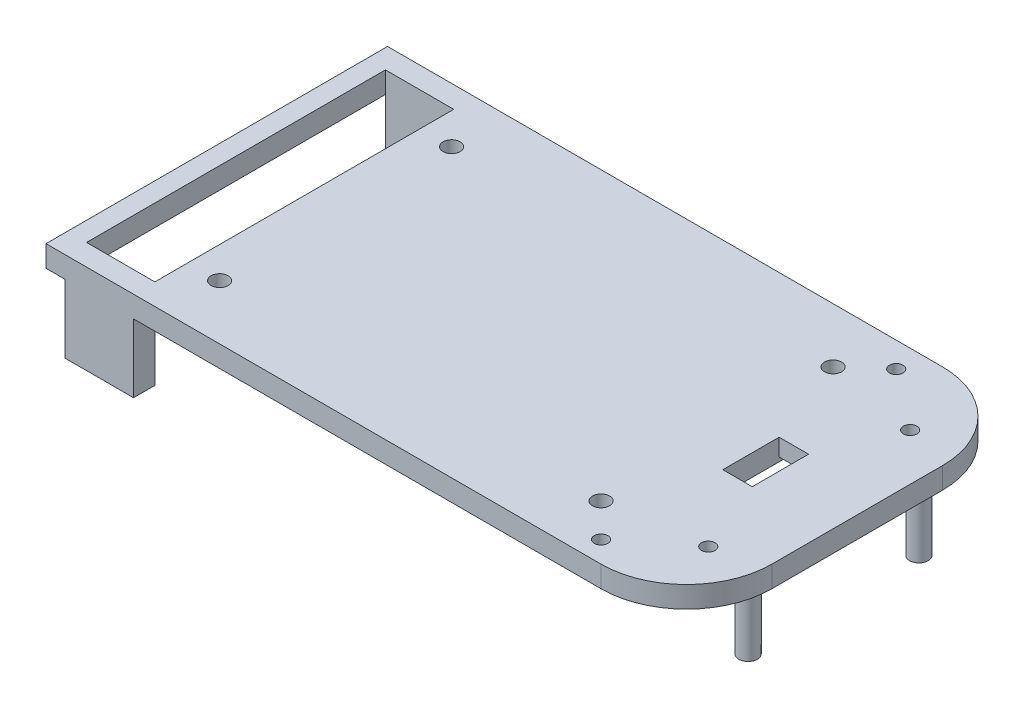
SolidWorks part; units mm, degrees
note: The reader was unsure of these and kept them because the rebuilt part matched: shared geometry of "Croquis2<3>", "Croquis4<3>".
ref_plane "Front Plane" through (0, 0, 0) normal (0, 0, 1) x (1, 0, 0)
ref_plane "Top Plane" through (0, 0, 0) normal (0, 1, 0) x (1, 0, 0)
ref_plane "Right Plane" through (0, 0, 0) normal (1, 0, 0) x (0, 0, -1)
sketch "Croquis2" plane through (0, 0, 0) normal (0, 1, 0) x (1, 0, 0)
  line L0 (45, 0) -> (46.0553, 0) construction
  line L1 (-75, -40) -> (55, -40)
  line L2 (-75, -40) -> (-75, 40)
  line L3 (-75, 40) -> (55, 40)
  line L4 (75, -20) -> (75, 20)
  line L5 (45, 0) -> (46.0553, 0) construction
  line L6 (67, 26.7583) -> (67, -26.7583)
  line L7 (45, -30) -> (-50, -30)
  line L8 (45, -30) -> (45, 30)
  line L9 (45, 30) -> (-50, 30)
  line L10 (-50, -30) -> (-50, 30)
  line L11 (67, -26.7583) -> (67, 26.7583)
  line L13 (67, 26.7583) -> (61, 26.7583)
  line L15 (46.228, -1.6) -> (46.2586, -1.7343)
  line L16 (61.1553, 0) -> (61.0553, 0) construction
  line L17 (54.1602, 2.3742) -> (54.0439, 2.2986)
  line L18 (54.0439, 2.2986) -> (53.9684, 2.4149)
  line L19 (53.9087, 2.4244) -> (53.801, 2.3371)
  line L20 (53.801, 2.3371) -> (53.7137, 2.4449)
  line L21 (53.6534, 2.448) -> (53.5553, 2.35)
  line L22 (53.5553, 2.35) -> (53.4573, 2.448)
  line L23 (53.3969, 2.4449) -> (53.3097, 2.3371)
  line L24 (53.3097, 2.3371) -> (53.2019, 2.4244)
  line L25 (53.1422, 2.4149) -> (53.0667, 2.2986)
  line L26 (53.0667, 2.2986) -> (52.9505, 2.3742)
  line L27 (52.8921, 2.3585) -> (52.8291, 2.235)
  line L28 (52.8291, 2.235) -> (52.7056, 2.2979)
  line L29 (52.6492, 2.2763) -> (52.5995, 2.1468)
  line L30 (52.5995, 2.1468) -> (52.4701, 2.1965)
  line L31 (52.4162, 2.1691) -> (52.3803, 2.0352)
  line L32 (52.3803, 2.0352) -> (52.2464, 2.071)
  line L33 (52.1957, 2.0381) -> (52.174, 1.9012)
  line L34 (52.174, 1.9012) -> (52.0371, 1.9229)
  line L35 (51.9901, 1.8848) -> (51.9829, 1.7464)
  line L36 (51.9829, 1.7464) -> (51.8444, 1.7536)
  line L37 (51.8017, 1.7109) -> (51.8089, 1.5725)
  line L38 (51.8089, 1.5725) -> (51.6705, 1.5652)
  line L39 (51.6325, 1.5182) -> (51.6541, 1.3813)
  line L40 (51.6541, 1.3813) -> (51.5172, 1.3596)
  line L41 (51.4843, 1.3089) -> (51.5202, 1.175)
  line L42 (51.5202, 1.175) -> (51.3862, 1.1391)
  line L43 (51.3588, 1.0853) -> (51.4085, 0.9558)
  line L44 (51.4085, 0.9558) -> (51.2791, 0.9061)
  line L45 (51.2574, 0.8497) -> (51.3203, 0.7262)
  line L46 (51.3203, 0.7262) -> (51.1968, 0.6632)
  line L47 (51.1812, 0.6049) -> (51.2567, 0.4886)
  line L48 (51.2567, 0.4886) -> (51.1404, 0.4131)
  line L49 (51.1309, 0.3534) -> (51.2182, 0.2456)
  line L50 (51.2182, 0.2456) -> (51.1105, 0.1584)
  line L51 (51.1073, 0.098) -> (51.2053, 0)
  line L52 (51.2053, 0) -> (51.1073, -0.098)
  line L53 (51.1105, -0.1584) -> (51.2182, -0.2456)
  line L54 (51.2182, -0.2456) -> (51.1309, -0.3534)
  line L55 (51.1404, -0.4131) -> (51.2567, -0.4886)
  line L56 (51.2567, -0.4886) -> (51.1812, -0.6049)
  line L57 (51.1968, -0.6632) -> (51.3203, -0.7262)
  line L58 (51.3203, -0.7262) -> (51.2574, -0.8497)
  line L59 (51.2791, -0.9061) -> (51.4085, -0.9558)
  line L60 (51.4085, -0.9558) -> (51.3588, -1.0853)
  line L61 (51.3862, -1.1391) -> (51.5202, -1.175)
  line L62 (51.5202, -1.175) -> (51.4843, -1.3089)
  line L63 (51.5172, -1.3596) -> (51.6541, -1.3813)
  line L64 (51.6541, -1.3813) -> (51.6325, -1.5182)
  line L65 (51.6705, -1.5652) -> (51.8089, -1.5725)
  line L66 (51.8089, -1.5725) -> (51.8017, -1.7109)
  line L67 (51.8444, -1.7536) -> (51.9829, -1.7464)
  line L68 (51.9829, -1.7464) -> (51.9901, -1.8848)
  line L69 (52.0371, -1.9229) -> (52.174, -1.9012)
  line L70 (52.174, -1.9012) -> (52.1957, -2.0381)
  line L71 (52.2464, -2.071) -> (52.3803, -2.0352)
  line L72 (52.3803, -2.0352) -> (52.4162, -2.1691)
  line L73 (52.4701, -2.1965) -> (52.5995, -2.1468)
  line L74 (52.5995, -2.1468) -> (52.6492, -2.2763)
  line L75 (52.7056, -2.2979) -> (52.8291, -2.235)
  line L76 (52.8291, -2.235) -> (52.8921, -2.3585)
  line L77 (52.9505, -2.3742) -> (53.0667, -2.2986)
  line L78 (53.0667, -2.2986) -> (53.1422, -2.4149)
  line L79 (53.2019, -2.4244) -> (53.3097, -2.3371)
  line L80 (53.3097, -2.3371) -> (53.3969, -2.4449)
  line L81 (53.4573, -2.448) -> (53.5553, -2.35)
  line L82 (53.5553, -2.35) -> (53.6534, -2.448)
  line L83 (53.7137, -2.4449) -> (53.801, -2.3371)
  line L84 (53.801, -2.3371) -> (53.9087, -2.4244)
  line L85 (53.9684, -2.4149) -> (54.0439, -2.2986)
  line L86 (54.0439, -2.2986) -> (54.1602, -2.3742)
  line L87 (54.2186, -2.3585) -> (54.2815, -2.235)
  line L88 (54.2815, -2.235) -> (54.4051, -2.2979)
  line L89 (54.4615, -2.2763) -> (54.5112, -2.1468)
  line L90 (54.5112, -2.1468) -> (54.6406, -2.1965)
  line L91 (54.6944, -2.1691) -> (54.7303, -2.0352)
  line L92 (54.7303, -2.0352) -> (54.8643, -2.071)
  line L93 (54.9149, -2.0381) -> (54.9366, -1.9012)
  line L94 (54.9366, -1.9012) -> (55.0736, -1.9229)
  line L95 (55.1205, -1.8848) -> (55.1278, -1.7464)
  line L96 (55.1278, -1.7464) -> (55.2662, -1.7536)
  line L97 (55.309, -1.7109) -> (55.3017, -1.5725)
  line L98 (55.3017, -1.5725) -> (55.4402, -1.5652)
  line L99 (55.4782, -1.5182) -> (55.4565, -1.3813)
  line L100 (55.4565, -1.3813) -> (55.5935, -1.3596)
  line L101 (55.6264, -1.3089) -> (55.5905, -1.175)
  line L102 (55.5905, -1.175) -> (55.7244, -1.1391)
  line L103 (55.7518, -1.0853) -> (55.7022, -0.9558)
  line L104 (55.7022, -0.9558) -> (55.8316, -0.9061)
  line L105 (55.8533, -0.8497) -> (55.7903, -0.7262)
  line L106 (55.7903, -0.7262) -> (55.9138, -0.6632)
  line L107 (55.9295, -0.6049) -> (55.854, -0.4886)
  line L108 (55.854, -0.4886) -> (55.9703, -0.4131)
  line L109 (55.9797, -0.3534) -> (55.8925, -0.2456)
  line L110 (55.8925, -0.2456) -> (56.0002, -0.1584)
  line L111 (56.0034, -0.098) -> (55.9053, 0)
  line L112 (55.9053, 0) -> (56.0034, 0.098)
  line L113 (56.0002, 0.1584) -> (55.8925, 0.2456)
  line L114 (55.8925, 0.2456) -> (55.9797, 0.3534)
  line L115 (55.9703, 0.4131) -> (55.854, 0.4886)
  line L116 (55.854, 0.4886) -> (55.9295, 0.6049)
  line L117 (55.9138, 0.6632) -> (55.7903, 0.7262)
  line L118 (55.7903, 0.7262) -> (55.8533, 0.8497)
  line L119 (55.8316, 0.9061) -> (55.7022, 0.9558)
  line L120 (55.7022, 0.9558) -> (55.7518, 1.0853)
  line L121 (55.7244, 1.1391) -> (55.5905, 1.175)
  line L122 (55.5905, 1.175) -> (55.6264, 1.3089)
  line L123 (55.5935, 1.3596) -> (55.4565, 1.3813)
  line L124 (55.4565, 1.3813) -> (55.4782, 1.5182)
  line L125 (55.4402, 1.5652) -> (55.3017, 1.5725)
  line L126 (55.3017, 1.5725) -> (55.309, 1.7109)
  line L127 (55.2662, 1.7536) -> (55.1278, 1.7464)
  line L128 (55.1278, 1.7464) -> (55.1205, 1.8848)
  line L129 (55.0736, 1.9229) -> (54.9366, 1.9012)
  line L130 (54.9366, 1.9012) -> (54.9149, 2.0381)
  line L131 (54.8643, 2.071) -> (54.7303, 2.0352)
  line L132 (54.7303, 2.0352) -> (54.6944, 2.1691)
  line L133 (54.6406, 2.1965) -> (54.5112, 2.1468)
  line L134 (54.5112, 2.1468) -> (54.4615, 2.2763)
  line L135 (54.4051, 2.2979) -> (54.2815, 2.235)
  line L136 (54.2815, 2.235) -> (54.2186, 2.3585)
  line L137 (53.5553, 0) -> (53.5553, -7.5) construction
  line L139 (65.0006, 25.8237) -> (59.5501, 25.8237) construction
  line L141 (61.0553, 0) -> (67, 0) construction
  line L142 (59.0553, 0) -> (53.5553, 0) construction
  line L143 (48.0553, 0) -> (53.5553, 0) construction
  line L144 (48.0553, 0) -> (59.0553, 0) construction
  line L145 (60.701, 2.278) -> (60.8827, 1.6)
  line L146 (61, 24.889) -> (61, 23.889)
  line L149 (61, 22.0197) -> (61, 21.0197)
  line L152 (61, 19.1504) -> (61, 18.1504)
  line L154 (59.5501, 17.5667) -> (59.5501, 16.8648)
  line L155 (61, 16.2811) -> (61, 15.2811)
  line L157 (59.5501, 14.6974) -> (59.5501, 13.9955)
  line L158 (61, 13.4118) -> (61, 12.4118)
  line L160 (59.5501, 11.8282) -> (59.5501, 11.1262)
  line L161 (61, 10.5425) -> (61, 9.5425)
  line L163 (59.5501, 8.9589) -> (59.5501, 8.2569)
  line L164 (61, 7.6732) -> (61, 6.6732)
  line L166 (59.5501, 6.0896) -> (59.5501, 5.3876)
  line L167 (61, 4.8039) -> (61, 3.8039)
  line L169 (59.5501, 3.2203) -> (59.5501, 2.5183)
  line L170 (61, 1.9346) -> (61, 0.9346)
  line L172 (59.5501, 0.351) -> (59.5501, -0.351)
  line L173 (61, -0.9346) -> (61, -1.9346)
  line L175 (59.5501, -2.5183) -> (59.5501, -3.2203)
  line L176 (61, -3.8039) -> (61, -4.8039)
  line L178 (59.5501, -5.3876) -> (59.5501, -6.0896)
  line L179 (61, -6.6732) -> (61, -7.6732)
  line L181 (59.5501, -8.2569) -> (59.5501, -8.9589)
  line L182 (61, -9.5425) -> (61, -10.5425)
  line L184 (59.5501, -11.1262) -> (59.5501, -11.8282)
  line L185 (61, -12.4118) -> (61, -13.4118)
  line L187 (59.5501, -13.9955) -> (59.5501, -14.6974)
  line L188 (61, -15.2811) -> (61, -16.2811)
  line L190 (59.5501, -16.8648) -> (59.5501, -17.5667)
  line L191 (61, -18.1504) -> (61, -19.1504)
  line L194 (61, -21.0197) -> (61, -22.0197)
  line L197 (61, -23.889) -> (61, -24.889)
  line L200 (64, 26.7583) -> (64, 26.3977) construction
  line L203 (61, -26.7583) -> (67, -26.7583)
  line L204 (75, 20) -> (67, 20) construction
  line L205 (61, -26.7583) -> (61, -27.7583) [skipped]
  line L206 (-50, 0) -> (-75, 0) construction
  line L207 (75, -20) -> (67, -20) construction
  line L208 (50, -40) -> (50, 40) construction
  line L209 (50, -35) -> (50, -43.5216) construction
  line L210 (53.5731, -35) -> (53.5731, -43.5216)
  line L211 (46.4269, -35) -> (46.4269, -43.5216)
  line L212 (50.0036, 34.1275) -> (50.0036, 40.0656) construction
  line L213 (53.6852, 34.1275) -> (53.5731, 43.5216)
  line L214 (46.4269, 35) -> (46.4269, 43.5216)
  line L215 (-50, -30) -> (-47.1716, -27.1716) construction
  line L221 (-50, -30) -> (-47.1716, -30)
  line L222 (-50, -30) -> (-50, -27.1716)
  line L223 (46.4269, -43.5216) -> (46.4269, -48.5216)
  line L224 (53.5731, -43.5216) -> (53.5731, -48.5216)
  line L225 (46.4269, -48.5216) -> (53.5731, -48.5216)
  line L226 (53.5731, 43.5216) -> (53.5731, 48.5216)
  line L227 (46.4269, 43.5216) -> (46.4269, 48.5216)
  line L228 (46.4269, 48.5216) -> (53.5731, 48.5216)
  line L229 (50, 43.0304) -> (64, 23.3977) construction
  line L232 (46.4269, 48.5216) -> (53.5731, 48.5216)
  line L233 (46.4269, 48.5216) -> (46.4269, 46.5216)
  line L234 (53.5731, 48.5216) -> (53.5731, 46.5216)
  line L235 (46.4269, 46.5216) -> (53.5731, 46.5216)
  line L236 (46.4269, -46.5216) -> (53.5731, -46.5216)
  line L239 (61, 19.1504) -> (67, 19.1504)
  line L240 (61, 26.7583) -> (61, 19.1504)
  line L241 (50.0036, 40.0656) -> (61.1732, 24.4022)
  line L242 (52.8363, 42.0529) -> (64, 26.3977)
  line L243 (48.6009, 42.0327) -> (62.6009, 22.4) construction
  line L244 (51.4182, 44.0416) -> (65.4182, 24.409) construction
  line L245 (61, 24.889) -> (61, 26.7583)
  line L246 (64, 25.8237) -> (64, -26.7583) construction
  line L248 (-70.5, -35) -> (-54.5, -35)
  line L249 (61, -26.7583) -> (61, -19.1504)
  line L250 (61, -19.1504) -> (67, -19.1504)
  line L251 (-50, -27.1716) -> (-47.1716, -27.1716)
  line L252 (-47.1716, -30) -> (-47.1716, -27.1716)
  line L253 (-2.5, -30) -> (-2.5, 30) construction
  line L254 (-70.5, -35) -> (-70.5, -40)
  line L255 (-54.5, 35) -> (-70.5, 35)
  line L260 (-54.5, 35) -> (-54.5, -35)
  line L261 (-54.5, -35) -> (-70.5, -35)
  line L262 (-70.5, 35) -> (-70.5, -35)
  line L263 (-54.5, 35) -> (-70.5, -35) construction
  line L264 (-54.5, -35) -> (-70.5, 35) construction
  line L265 (-70.5, -40) -> (-54.5, -40)
  line L266 (-54.5, -35) -> (-54.5, -40)
  line L267 (-70.5, 35) -> (-54.5, 35)
  line L268 (-70.5, 35) -> (-70.5, 40)
  line L269 (-70.5, 40) -> (-54.5, 40)
  line L270 (-54.5, 35) -> (-54.5, 40)
  circle A0 centre (53.5553, 0) radius 7.5
  arc A1 (53.9684, 2.4149) -> (53.9087, 2.4244) centre (53.5553, 0) ccw
  arc A2 (53.7137, 2.4449) -> (53.6534, 2.448) centre (53.5553, 0) ccw
  arc A3 (53.4573, 2.448) -> (53.3969, 2.4449) centre (53.5553, 0) ccw
  arc A4 (53.2019, 2.4244) -> (53.1422, 2.4149) centre (53.5553, 0) ccw
  arc A5 (52.9505, 2.3742) -> (52.8921, 2.3585) centre (53.5553, 0) ccw
  arc A6 (52.7056, 2.2979) -> (52.6492, 2.2763) centre (53.5553, 0) ccw
  arc A7 (52.4701, 2.1965) -> (52.4162, 2.1691) centre (53.5553, 0) ccw
  arc A8 (52.2464, 2.071) -> (52.1957, 2.0381) centre (53.5553, 0) ccw
  arc A9 (52.0371, 1.9229) -> (51.9901, 1.8848) centre (53.5553, 0) ccw
  arc A10 (51.8444, 1.7536) -> (51.8017, 1.7109) centre (53.5553, 0) ccw
  arc A11 (51.6705, 1.5652) -> (51.6325, 1.5182) centre (53.5553, 0) ccw
  arc A12 (51.5172, 1.3596) -> (51.4843, 1.3089) centre (53.5553, 0) ccw
  arc A13 (51.3862, 1.1391) -> (51.3588, 1.0853) centre (53.5553, 0) ccw
  arc A14 (51.2791, 0.9061) -> (51.2574, 0.8497) centre (53.5553, 0) ccw
  arc A15 (51.1968, 0.6632) -> (51.1812, 0.6049) centre (53.5553, 0) ccw
  arc A16 (51.1404, 0.4131) -> (51.1309, 0.3534) centre (53.5553, 0) ccw
  arc A17 (51.1105, 0.1584) -> (51.1073, 0.098) centre (53.5553, 0) ccw
  arc A18 (51.1073, -0.098) -> (51.1105, -0.1584) centre (53.5553, 0) ccw
  arc A19 (51.1309, -0.3534) -> (51.1404, -0.4131) centre (53.5553, 0) ccw
  arc A20 (51.1812, -0.6049) -> (51.1968, -0.6632) centre (53.5553, 0) ccw
  arc A21 (51.2574, -0.8497) -> (51.2791, -0.9061) centre (53.5553, 0) ccw
  arc A22 (51.3588, -1.0853) -> (51.3862, -1.1391) centre (53.5553, 0) ccw
  arc A23 (51.4843, -1.3089) -> (51.5172, -1.3596) centre (53.5553, 0) ccw
  arc A24 (51.6325, -1.5182) -> (51.6705, -1.5652) centre (53.5553, 0) ccw
  arc A25 (51.8017, -1.7109) -> (51.8444, -1.7536) centre (53.5553, 0) ccw
  arc A26 (51.9901, -1.8848) -> (52.0371, -1.9229) centre (53.5553, 0) ccw
  arc A27 (52.1957, -2.0381) -> (52.2464, -2.071) centre (53.5553, 0) ccw
  arc A28 (52.4162, -2.1691) -> (52.4701, -2.1965) centre (53.5553, 0) ccw
  arc A29 (52.6492, -2.2763) -> (52.7056, -2.2979) centre (53.5553, 0) ccw
  arc A30 (52.8921, -2.3585) -> (52.9505, -2.3742) centre (53.5553, 0) ccw
  arc A31 (53.1422, -2.4149) -> (53.2019, -2.4244) centre (53.5553, 0) ccw
  arc A32 (53.3969, -2.4449) -> (53.4573, -2.448) centre (53.5553, 0) ccw
  arc A33 (53.6534, -2.448) -> (53.7137, -2.4449) centre (53.5553, 0) ccw
  arc A34 (53.9087, -2.4244) -> (53.9684, -2.4149) centre (53.5553, 0) ccw
  arc A35 (54.1602, -2.3742) -> (54.2186, -2.3585) centre (53.5553, 0) ccw
  arc A36 (54.4051, -2.2979) -> (54.4615, -2.2763) centre (53.5553, 0) ccw
  arc A37 (54.6406, -2.1965) -> (54.6944, -2.1691) centre (53.5553, 0) ccw
  arc A38 (54.8643, -2.071) -> (54.9149, -2.0381) centre (53.5553, 0) ccw
  arc A39 (55.0736, -1.9229) -> (55.1205, -1.8848) centre (53.5553, 0) ccw
  arc A40 (55.2662, -1.7536) -> (55.309, -1.7109) centre (53.5553, 0) ccw
  arc A41 (55.4402, -1.5652) -> (55.4782, -1.5182) centre (53.5553, 0) ccw
  arc A42 (55.5935, -1.3596) -> (55.6264, -1.3089) centre (53.5553, 0) ccw
  arc A43 (55.7244, -1.1391) -> (55.7518, -1.0853) centre (53.5553, 0) ccw
  arc A44 (55.8316, -0.9061) -> (55.8533, -0.8497) centre (53.5553, 0) ccw
  arc A45 (55.9138, -0.6632) -> (55.9295, -0.6049) centre (53.5553, 0) ccw
  arc A46 (55.9703, -0.4131) -> (55.9797, -0.3534) centre (53.5553, 0) ccw
  arc A47 (56.0002, -0.1584) -> (56.0034, -0.098) centre (53.5553, 0) ccw
  arc A48 (56.0034, 0.098) -> (56.0002, 0.1584) centre (53.5553, 0) ccw
  arc A49 (55.9797, 0.3534) -> (55.9703, 0.4131) centre (53.5553, 0) ccw
  arc A50 (55.9295, 0.6049) -> (55.9138, 0.6632) centre (53.5553, 0) ccw
  arc A51 (55.8533, 0.8497) -> (55.8316, 0.9061) centre (53.5553, 0) ccw
  arc A52 (55.7518, 1.0853) -> (55.7244, 1.1391) centre (53.5553, 0) ccw
  arc A53 (55.6264, 1.3089) -> (55.5935, 1.3596) centre (53.5553, 0) ccw
  arc A54 (55.4782, 1.5182) -> (55.4402, 1.5652) centre (53.5553, 0) ccw
  arc A55 (55.309, 1.7109) -> (55.2662, 1.7536) centre (53.5553, 0) ccw
  arc A56 (55.1205, 1.8848) -> (55.0736, 1.9229) centre (53.5553, 0) ccw
  arc A57 (54.9149, 2.0381) -> (54.8643, 2.071) centre (53.5553, 0) ccw
  arc A58 (54.6944, 2.1691) -> (54.6406, 2.1965) centre (53.5553, 0) ccw
  arc A59 (54.4615, 2.2763) -> (54.4051, 2.2979) centre (53.5553, 0) ccw
  arc A60 (54.2186, 2.3585) -> (54.1602, 2.3742) centre (53.5553, 0) ccw
  circle A61 centre (53.5553, 0) radius 2.25
  arc A62 (55, 40) -> (75, 20) centre (55, 20) cw
  arc A63 (55, -40) -> (75, -20) centre (55, -20) ccw
  circle A64 centre (53.5553, 0) radius 5.5
  arc A65 (54.0553, -5.4772) -> (55.1553, -7.3273) centre (59.6317, -3.4139) ccw
  arc A66 (53.0553, -5.4772) -> (51.9553, -7.3273) centre (47.479, -3.4139) cw
  arc A67 (50.3837, -4.4934) -> (48.506, -5.5457) centre (46.5861, 0.0817) cw
  arc A68 (51.2497, -4.9934) -> (51.2773, -7.1457) centre (57.1107, -5.9946) ccw
  arc A69 (48.5619, -2.3056) -> (46.4097, -2.278) centre (47.5607, 3.5553) cw
  arc A70 (49.0619, -3.1716) -> (48.0097, -5.0493) centre (53.637, -6.9692) ccw
  arc A71 (48.0781, 0.5) -> (46.228, 1.6) centre (50.1415, 6.0763) cw
  arc A72 (48.0781, -0.5) -> (46.228, -1.6) centre (50.1415, -6.0763) ccw
  arc A73 (49.0619, 3.1716) -> (48.0097, 5.0493) centre (53.637, 6.9692) cw
  arc A74 (48.5619, 2.3056) -> (46.4097, 2.278) centre (47.5607, -3.5553) ccw
  arc A75 (51.2497, 4.9934) -> (51.2773, 7.1457) centre (57.1107, 5.9946) cw
  arc A76 (50.3837, 4.4934) -> (48.506, 5.5457) centre (46.5861, -0.0817) ccw
  arc A77 (54.0553, 5.4772) -> (55.1553, 7.3273) centre (59.6317, 3.4139) cw
  arc A78 (53.0553, 5.4772) -> (51.9553, 7.3273) centre (47.479, 3.4139) ccw
  arc A79 (56.727, 4.4934) -> (58.6046, 5.5457) centre (60.5245, -0.0817) cw
  arc A80 (55.8609, 4.9934) -> (55.8334, 7.1457) centre (50, 5.9946) ccw
  arc A81 (58.5487, 2.3056) -> (60.701, 2.278) centre (59.55, -3.5553) cw
  arc A82 (58.0487, 3.1716) -> (59.101, 5.0493) centre (53.4736, 6.9692) ccw
  arc A83 (59.0326, -0.5) -> (60.8827, -1.6) centre (56.9692, -6.0763) cw
  arc A84 (59.0326, 0.5) -> (60.8827, 1.6) centre (56.9692, 6.0763) ccw
  arc A85 (58.0487, -3.1716) -> (59.101, -5.0493) centre (53.4736, -6.9692) cw
  arc A86 (58.5487, -2.3056) -> (60.701, -2.278) centre (59.55, 3.5553) ccw
  arc A89 (55.8609, -4.9934) -> (55.8334, -7.1457) centre (50, -5.9946) cw
  arc A90 (56.727, -4.4934) -> (58.6046, -5.5457) centre (60.5245, 0.0817) ccw
  arc A95 (61, 16.2811) -> (59.5501, 16.8648) centre (62.2327, 21.4358) cw
  arc A96 (61, 18.1504) -> (59.5501, 17.5667) centre (62.2327, 12.9958) ccw
  arc A97 (61, 13.4118) -> (59.5501, 13.9955) centre (62.2327, 18.5665) cw
  arc A98 (61, 15.2811) -> (59.5501, 14.6974) centre (62.2327, 10.1265) ccw
  arc A99 (61, 10.5425) -> (59.5501, 11.1262) centre (62.2327, 15.6972) cw
  arc A100 (61, 12.4118) -> (59.5501, 11.8282) centre (62.2327, 7.2572) ccw
  arc A101 (61, 7.6732) -> (59.5501, 8.2569) centre (62.2327, 12.8279) cw
  arc A102 (61, 9.5425) -> (59.5501, 8.9589) centre (62.2327, 4.3879) ccw
  arc A103 (61, 4.8039) -> (59.5501, 5.3876) centre (62.2327, 9.9586) cw
  arc A104 (61, 6.6732) -> (59.5501, 6.0896) centre (62.2327, 1.5186) ccw
  arc A105 (61, 1.9346) -> (59.5501, 2.5183) centre (62.2327, 7.0893) cw
  arc A106 (61, 3.8039) -> (59.5501, 3.2203) centre (62.2327, -1.3507) ccw
  arc A107 (61, -0.9346) -> (59.5501, -0.351) centre (62.2327, 4.22) cw
  arc A108 (61, 0.9346) -> (59.5501, 0.351) centre (62.2327, -4.22) ccw
  arc A109 (61, -3.8039) -> (59.5501, -3.2203) centre (62.2327, 1.3507) cw
  arc A110 (61, -1.9346) -> (59.5501, -2.5183) centre (62.2327, -7.0893) ccw
  arc A111 (61, -6.6732) -> (59.5501, -6.0896) centre (62.2327, -1.5186) cw
  arc A112 (61, -4.8039) -> (59.5501, -5.3876) centre (62.2327, -9.9586) ccw
  arc A113 (61, -9.5425) -> (59.5501, -8.9589) centre (62.2327, -4.3879) cw
  arc A114 (61, -7.6732) -> (59.5501, -8.2569) centre (62.2327, -12.8279) ccw
  arc A115 (61, -12.4118) -> (59.5501, -11.8282) centre (62.2327, -7.2572) cw
  arc A116 (61, -10.5425) -> (59.5501, -11.1262) centre (62.2327, -15.6972) ccw
  arc A117 (61, -15.2811) -> (59.5501, -14.6974) centre (62.2327, -10.1265) cw
  arc A118 (61, -13.4118) -> (59.5501, -13.9955) centre (62.2327, -18.5665) ccw
  arc A119 (61, -18.1504) -> (59.5501, -17.5667) centre (62.2327, -12.9958) cw
  arc A120 (61, -16.2811) -> (59.5501, -16.8648) centre (62.2327, -21.4358) ccw
  circle A128 centre (64, -23.889) radius 1.5875
  circle A129 centre (64, 23.3977) radius 1.5875
  circle A130 centre (69.4482, 20) radius 2.175
  circle A131 centre (69.4482, -20) radius 2.175
  circle A132 centre (50, -35) radius 1.5875
  circle A133 centre (50.0036, 34.1275) radius 1.5875
  arc A134 (53.5731, -35) -> (46.4269, -35) centre (50, -35) ccw
  arc A136 (53.6852, 34.1275) -> (46.4269, 35) centre (50.0036, 34.1275) cw
  circle A138 centre (50, 43.0304) radius 1.7203
  circle A139 centre (50, -43.5216) radius 1.7203
  arc A142 (52.4426, 44.7721) -> (47.5574, 41.2886) centre (50, 43.0304) ccw
  arc A143 (61.5574, 21.6559) -> (66.4426, 25.1395) centre (64, 23.3977) ccw
  arc A144 (52.8363, 42.0529) -> (50.0286, 40.0305) centre (50, 43.0304) ccw
  arc A145 (61.1732, 24.4022) -> (64, 26.3977) centre (64, 23.3977) ccw
  arc A146 (62.2582, 25.8403) -> (62.2351, 25.8237) centre (64, 23.3977) ccw
  circle A151 centre (-47.1716, -27.1716) radius 2
  circle A152 centre (42.1716, -27.1716) radius 2
  circle A153 centre (42.1716, 27.1716) radius 2
  circle A154 centre (-47.1716, 27.1716) radius 2
  point P5 (65.0006, 25.8237)
  point P6 (0, 0)
  point P13 (67, 0)
  point P20 (59.8563, -29.3308)
  point P216 (53.5553, -7.5)
  point P221 (53.5553, -5.5)
  point P283 (53.5553, 0)
  point P290 (59.5501, 25.8237)
  point P292 (61, 24.889)
  point P297 (53.5553, 0)
  point P409 (-62.5, 0)
  point P411 (-62.5, 0)
  point P415 (-62.5, 0)
  point P424 (50, -39.2608)
  point P434 (50, 39.2608)
  point P453 (57, 33.214)
  dimension "D6" = 15
  dimension "D9" = 6
  dimension "D10" = 11
  dimension "D13" = 30
  dimension "D20" = 1
  dimension "D22" = 3.175
  dimension "D23" = 3.175
  dimension "D8" = 4.35
  dimension "D25" = 3.175
  dimension "D30" = 5
  dimension "D32" = 3
  dimension "D33" = 5.5518
  dimension "D18" = 4
  dimension "D2" = 80
  dimension "D3" = 30
  dimension "D4" = 60
  dimension "D5" = 12
  dimension "D7" = 8.5553
  dimension "D11" = 0.5
  dimension "D12" = 1.6
  dimension "D14" = 4
  dimension "D15" = 95
  dimension "2.25" = 22
  dimension "D16" = 1.8693
  dimension "D17" = 1.8693
  dimension "D19" = 0.702
  dimension "D24" = 16
  dimension "D26" = 5
  dimension "D27" = 5
  dimension "D28" = 130
  dimension "D29" = 5.5518
  dimension "D31" = 2
  dimension "D21" = 19
extrude "Saliente-Extruir1" add sketch "Croquis2" against normal blind 5
extrude "Saliente-Extruir2" add sketch "Croquis2<3>" against normal blind 21 contours L255 L270 L3 L268 | L266 L248 L254 L1 | A130 | A131
sketch "Croquis2<3>" plane through (0, 0, 0) normal (0, 1, 0) x (1, 0, 0) same geometry as "Croquis2"
sketch "Croquis3" plane through (0, -5, 0) normal (0, -1, 0) x (1, 0, 0)
  circle A0 centre (53.5553, 0) radius 2.45
sketch "Croquis4" plane through (0, -5, 0) normal (0, -1, 0) x (1, 0, 0)
  line L1 (57.0066, -6.5906) -> (50.1041, -6.5906)
  line L2 (57.0066, -6.5906) -> (57.0066, 6.5906)
  line L3 (57.0066, 6.5906) -> (50.1041, 6.5906)
  line L4 (50.1041, -6.5906) -> (50.1041, 6.5906)
  line L5 (57.0066, -6.5906) -> (50.1041, 6.5906) construction
  line L6 (57.0066, 6.5906) -> (50.1041, -6.5906) construction
  line L7 (57.0066, -8.8903) -> (50.1041, -8.8903)
  line L8 (57.0066, -8.8903) -> (57.0066, 8.8903)
  line L9 (57.0066, 8.8903) -> (50.1041, 8.8903)
  line L10 (50.1041, -8.8903) -> (50.1041, 8.8903)
  line L11 (57.0066, -8.8903) -> (50.1041, 8.8903) construction
  line L12 (57.0066, 8.8903) -> (50.1041, -8.8903) construction
  point P0 (53.5553, 0)
  point P6 (53.5553, 0)
extrude "Cortar-Extruir1" cut sketch "Croquis4" against normal blind 5 contours L4 L1 L2 L3
extrude "Cortar-Extruir2" cut sketch "Croquis4<3>" against normal blind 1 contours L10 L3 L8 L9 | L10 L7 L8 L1
sketch "Croquis4<3>" plane through (0, -5, 0) normal (0, -1, 0) x (1, 0, 0) same geometry as "Croquis4"
